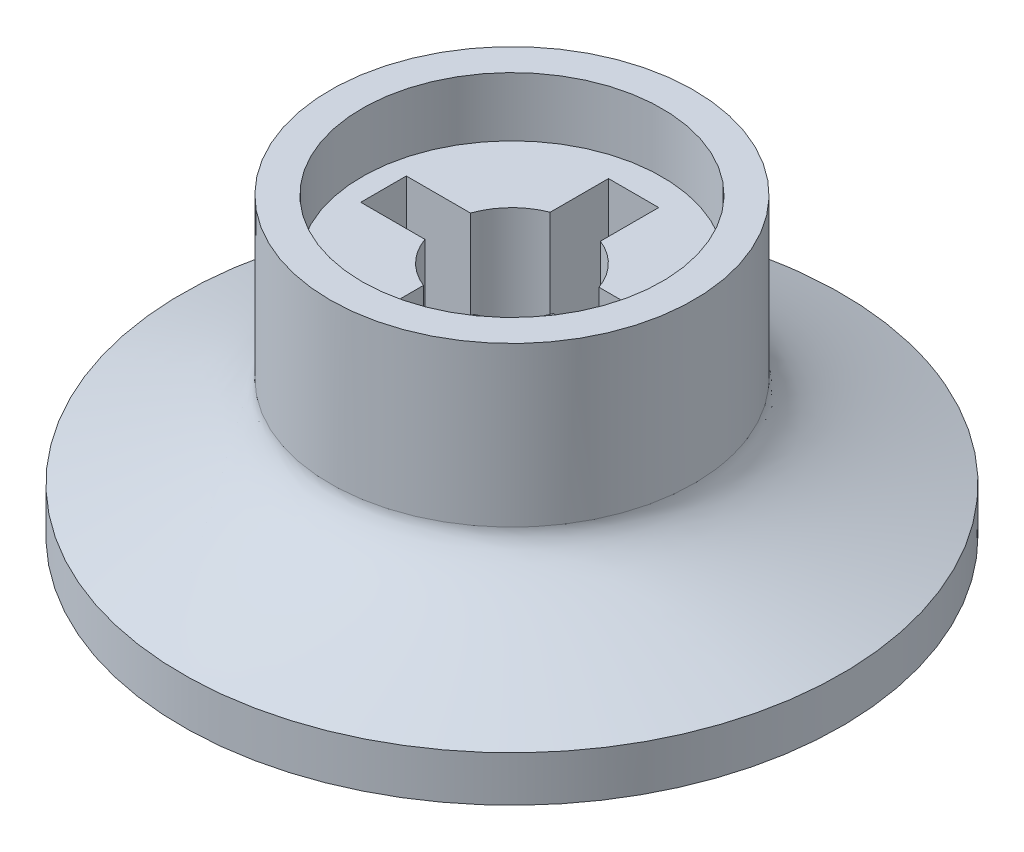
SolidWorks part; units mm, degrees
material "ABS"
ref_plane "Front Plane" through (0, 0, 0) normal (0, 0, 1) x (1, 0, 0)
ref_plane "Top Plane" through (0, 0, 0) normal (0, 1, 0) x (1, 0, 0)
ref_plane "Right Plane" through (0, 0, 0) normal (1, 0, 0) x (0, 0, -1)
sketch "Sketch1" plane through (0, 0, 0) normal (0, 1, 0) x (1, 0, 0)
  circle A0 centre (0, 0) radius 4
  dimension "D1" = 8
extrude "Boss-Extrude1" add sketch "Sketch1" along normal blind 3.5
sketch "Sketch2" plane through (0, 3.5, 0) normal (0, 1, 0) x (1, 0, 0)
  circle A0 centre (0, 0) radius 3.3
  circle A1 centre (0, 0) radius 4 construction
  dimension "D1" = 0.7
extrude "Cut-Extrude1" cut sketch "Sketch2" against normal blind 1.3
ref_plane "Plane1" through (0, -2, 0) normal (0, -1, 0) x (-1, 0, 0)
sketch "Sketch3" plane through (0, -2, 0) normal (0, -1, 0) x (-1, 0, 0)
  circle A0 centre (0, 0) radius 7.25
  dimension "D1" = 14.5
extrude "Boss-Extrude2" add sketch "Sketch3" along normal blind 1 separate body
loft "Loft1" add section face at (0, 0, 4) section face at (0, -2, -7.25) connector at (-3.4184, 0, 2.0771) connector at (-0.4325, -2, 7.2371)
sketch "Sketch4" plane through (0, 2.2, 0) normal (0, 1, 0) x (1, 0, 0)
  line L0 (-0.5523, 2.6761) -> (0.5523, 2.6761)
  line L1 (0.5523, 2.6761) -> (0.5523, 0.5012)
  line L2 (0.5523, 0.5012) -> (2.7647, 0.5012)
  line L3 (2.7647, 0.5012) -> (2.7647, -0.5012)
  line L4 (2.7647, -0.5012) -> (0.5523, -0.5012)
  line L5 (0.5523, -0.5012) -> (0.5523, -2.7614)
  line L6 (0.5523, -2.7614) -> (-0.5523, -2.7614)
  line L7 (-0.5523, -2.7614) -> (-0.5523, -0.5012)
  line L8 (-0.5523, -0.5012) -> (-2.8256, -0.5012)
  line L9 (-2.8256, -0.5012) -> (-2.8256, 0.5012)
  line L10 (-2.8256, 0.5012) -> (-0.5523, 0.5012)
  line L11 (-0.5523, 0.5012) -> (-0.5523, 2.6761)
  point P10 (-2.8256, 0)
  point P14 (2.7647, 0)
  point P16 (0, 2.6761)
  point P17 (0, -2.7614)
extrude "Cut-Extrude2" cut sketch "Sketch4" against normal through all both and the other way through all
sketch "Sketch5" plane through (0, 2.2, 0) normal (0, 1, 0) x (1, 0, 0)
  circle A0 centre (0, 0) radius 1.5
  dimension "D1" = 3
extrude "Cut-Extrude3" cut sketch "Sketch5" against normal through all
